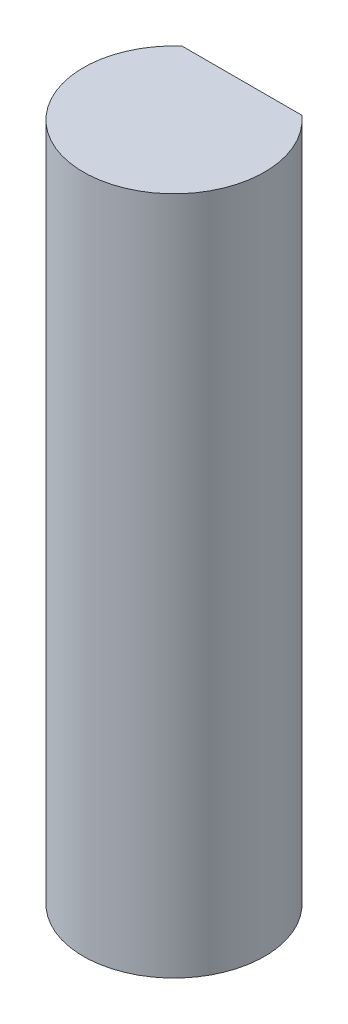
SolidWorks part; units mm, degrees
ref_plane "Front Plane" through (0, 0, 0) normal (0, 0, 1) x (1, 0, 0)
ref_plane "Top Plane" through (0, 0, 0) normal (0, 1, 0) x (1, 0, 0)
ref_plane "Right Plane" through (0, 0, 0) normal (1, 0, 0) x (0, 0, -1)
sketch "Sketch1" plane through (0, 0, 0) normal (0, 1, 0) x (1, 0, 0)
  line L0 (1.3229, 1.5) -> (-1.3229, 1.5)
  line L1 (-2.2, 0) -> (2.2, 0) construction
  arc A0 (-1.3229, 1.5) -> (1.3229, 1.5) centre (0, 0) ccw
  dimension "D1" = 2
  dimension "D2" = 1.5
extrude "Boss-Extrude1" add sketch "Sketch1" along normal mid plane 15
equation "\"height\" = 15"
equation "\"D1@Boss-Extrude1\"=\"height\""
